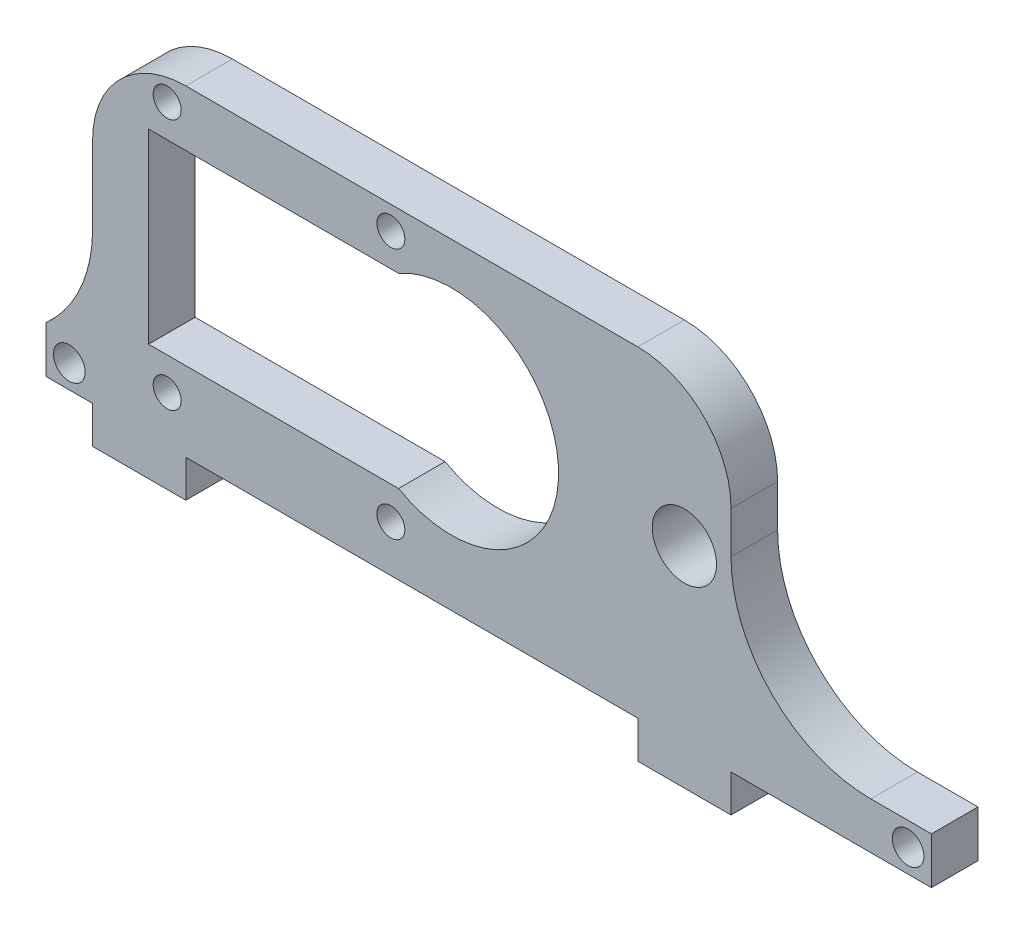
SolidWorks part; units mm, degrees
note: The reader was unsure of these and kept them because the rebuilt part matched: thickness of "Base-Flange1", "Sheet-Metal1".
ref_plane "Front Plane" through (0, 0, 0) normal (0, 0, 1) x (1, 0, 0)
ref_plane "Top Plane" through (0, 0, 0) normal (0, 1, 0) x (1, 0, 0)
ref_plane "Right Plane" through (0, 0, 0) normal (1, 0, 0) x (0, 0, -1)
sketch "Sketch1" plane through (0, 0, 0) normal (0, 0, 1) x (1, 0, 0)
  line L0 (-30.5, 13.5) -> (-6.5, 13.5) construction
  line L1 (-28.5, 16) -> (20, 16)
  line L2 (-38.5, 6) -> (-38.5, -13.5)
  line L3 (-28.5, -18.5) -> (20, -18.5)
  line L4 (30, 6) -> (30, -13.5)
  line L5 (-6.5, 13.5) -> (-6.5, -13.5) construction
  line L6 (-38.5, -18.5) -> (-28.5, -18.5) construction
  line L7 (-38.5, -18.5) -> (-28.5, -18.5) construction
  line L8 (-38.5, -18.5) -> (-38.5, -22.5)
  line L9 (-38.5, -22.5) -> (-28.5, -22.5)
  line L10 (-28.5, -18.5) -> (-28.5, -22.5)
  line L11 (30, -18.5) -> (20, -18.5) construction
  line L12 (30, -18.5) -> (30, -22.5)
  line L13 (30, -22.5) -> (20, -22.5)
  line L14 (20, -18.5) -> (20, -22.5)
  line L15 (20, -18.5) -> (30, -18.5) construction
  line L17 (-5.6789, 10) -> (-32.5, 10)
  line L18 (-5.6789, 10) -> (-5.6789, -10) construction
  line L19 (-5.6789, -10) -> (-32.5, -10)
  line L20 (-32.5, 10) -> (-32.5, -10)
  line L21 (51.5, -18.5) -> (30, -18.5)
  line L22 (51.5, -18.5) -> (51.5, -13.5)
  line L23 (51.5, -13.5) -> (30, -13.5)
  line L24 (30, -18.5) -> (30, -13.5) construction
  line L25 (-38.5, -18.5) -> (-43.5, -18.5)
  line L26 (-38.5, -18.5) -> (-38.5, -13.5) construction
  line L27 (-38.5, -13.5) -> (-43.5, -13.5)
  line L28 (-43.5, -18.5) -> (-43.5, -13.5)
  line L29 (30, -13.5) -> (30, -18.5) construction
  line L30 (-38.5, -13.5) -> (-38.5, -18.5) construction
  arc A0 (-5.6789, -10) -> (-5.6789, 10) centre (0, 0) ccw
  circle A1 centre (25, 0) radius 3.45
  circle A4 centre (-6.5, 13.5) radius 1.5
  circle A5 centre (-30.5, 13.5) radius 1.5
  circle A6 centre (-30.5, -13.5) radius 1.5
  circle A7 centre (-6.5, -13.5) radius 1.5
  arc A8 (20, 16) -> (30, 6) centre (20, 6) cw
  arc A9 (-28.5, 16) -> (-38.5, 6) centre (-28.5, 6) ccw
  arc A10 (-6.5, 9.4868) -> (-6.5, -9.4868) centre (0, 0) ccw construction
  arc A11 (-5.6789, 10) -> (-6.5, 9.4868) centre (0, 0) ccw construction
  arc A12 (-6.5, -9.4868) -> (-5.6789, -10) centre (0, 0) ccw construction
  circle A13 centre (-41, -16) radius 1.7
  circle A14 centre (49, -16) radius 1.7
  point P20 (-6.5, 0)
  point P39 (51.5, -16)
  point P40 (-43.5, -16)
  point P44 (-41, -18.5)
  dimension "D1" = 3
  dimension "D2" = 25
  dimension "D3" = 23
  dimension "D4" = 6.9
  dimension "D12" = 10
  dimension "D13" = 10
  dimension "D19" = 3.4
  dimension "D22" = 3.4
  dimension "D5" = 24
  dimension "D6" = 27
  dimension "D7" = 18.5
  dimension "D8" = 16
  dimension "D9" = 5
  dimension "D10" = 32
  dimension "D11" = 6.5
  dimension "D14" = 10
  dimension "D15" = 4
  dimension "D16" = 32.5
  dimension "D17" = 20
  dimension "D18" = 5
  dimension "D20" = 26.5
  dimension "D21" = 2.5
base flange "Base-Flange1" sketch "Sketch1" thickness 5 reverse thickness direction no parameters "D1"=0.7366
fillet "Fillet1" radius 15 1 edges at (30, -13.5, -2.5)
fillet "Fillet2" radius 15 1 edges at (-38.5, -13.5, -2.5)
sketch "Bend-Lines1" [suppressed] plane through (0, 0, 0) normal (0, 1, 0) x (1, 0, 0)
sketch "Bounding-Box1" [suppressed] plane through (0, 0, 0) normal (0, 1, 0) x (1, 0, 0)
sheet metal parameters "Sheet-Metal1" thickness 5 parameters "D1"=0.7366
flat pattern "Flat-Pattern1" [suppressed]
sketch "Bend-Lines2" plane through (0, 0, 0) normal (0, 1, 0) x (1, 0, 0)
sketch3d "Bounding-Box2" [suppressed]
  line L0 (-63.5, -28.5, 0) -> (26.5, -28.5, 0) construction
  line L1 (-63.5, 10, 0) -> (26.5, 10, 0) construction
  line L2 (-63.5, -28.5, 0) -> (-63.5, 10, 0) construction
  line L3 (26.5, -28.5, 0) -> (26.5, 10, 0) construction
